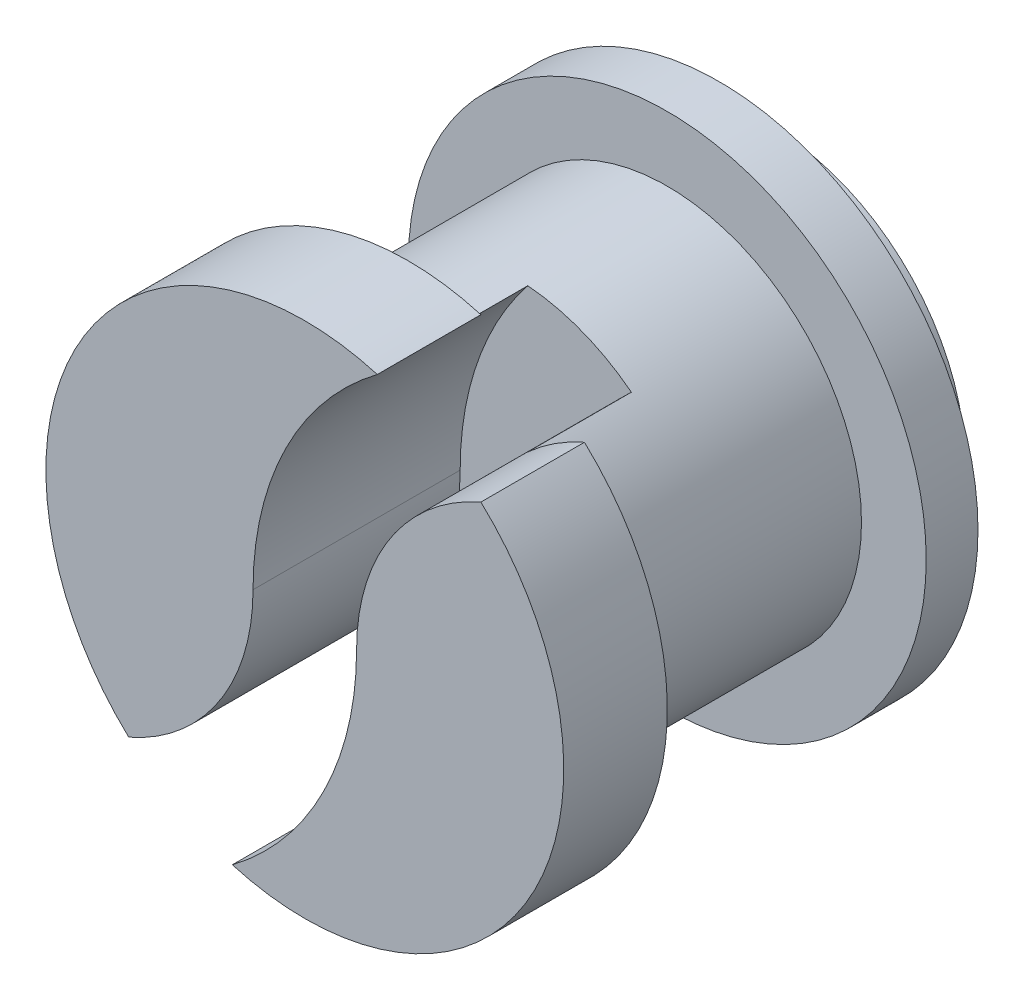
SolidWorks part; units mm, degrees
ref_plane "Спереди" through (0, 0, 0) normal (0, 0, 1) x (1, 0, 0)
ref_plane "Сверху" through (0, 0, 0) normal (0, 1, 0) x (1, 0, 0)
ref_plane "Справа" through (0, 0, 0) normal (1, 0, 0) x (0, 0, -1)
sketch "Эскиз1" plane through (0, 0, 0) normal (0, 0, 1) x (1, 0, 0)
  circle A0 centre (0, 0) radius 7.5
  dimension "D1" = 15
extrude "Бобышка-Вытянуть1" add sketch "Эскиз1" along normal blind 16
sketch "Эскиз2" plane through (0, 0, 0) normal (0, 0, 1) x (1, 0, 0)
  circle A0 centre (0, 0) radius 10
  dimension "D1" = 20
extrude "Бобышка-Вытянуть2" add sketch "Эскиз2" along normal blind 2 from offset 2
sketch "Эскиз5" plane through (0, 0, 0) normal (0, 0, 1) x (1, 0, 0)
  circle A0 centre (0, 0) radius 10
  dimension "D1" = 20
extrude "Бобышка-Вытянуть3" add sketch "Эскиз5" along normal blind 4 from offset 14
sketch "Эскиз9" plane through (0, 0, 0) normal (0, 0, 1) x (1, 0, 0)
  line L0 (0, -1000) -> (0, 49000) construction
  line L1 (2, -999.8394) -> (2, 49000.1606) construction
  line L2 (-2, -1000.2983) -> (-2, 48999.7017) construction
  line L3 (-1000, 0) -> (49000, 0) construction
  circle A9 centre (0, 0) radius 15
  arc A10 (9.05, 11.9623) -> (-2, 0) centre (10, 0) ccw
  arc A11 (13.05, 7.3958) -> (2, 0) centre (10, 0) ccw
  arc A12 (-13.05, -7.3958) -> (-2, 0) centre (-10, 0) ccw
  arc A13 (-9.05, -11.9623) -> (2, 0) centre (-10, 0) ccw
  dimension "D1" = 30
  dimension "D5" = 10
  dimension "D2" = 2
  dimension "D3" = 2
extrude "Вырез-Вытянуть3" cut sketch "Эскиз9" along normal blind 8 from offset 10 contours A9 A13 A11 A10 A12 region at (0, 0, 0)
sketch "Эскиз10" plane through (0, 0, 0) normal (0, 0, 1) x (1, 0, 0)
  circle A0 centre (0, 0) radius 6.5
  dimension "D1" = 13
extrude "Вырез-Вытянуть4" cut sketch "Эскиз10" along normal blind 3
sketch "Эскиз11" plane through (0, 0, 0) normal (0, 0, 1) x (1, 0, 0)
  line L1 (-5, -2.5) -> (5, -2.5)
  line L2 (-5, -2.5) -> (-5, 2.5)
  line L3 (-5, 2.5) -> (5, 2.5)
  line L4 (5, -2.5) -> (5, 2.5)
  line L5 (-5, -2.5) -> (5, 2.5) construction
  line L6 (-5, 2.5) -> (5, -2.5) construction
  point P0 (0, 0)
  dimension "D1" = 5
  dimension "D2" = 10
extrude "Вырез-Вытянуть5" cut sketch "Эскиз11" along normal blind 5
